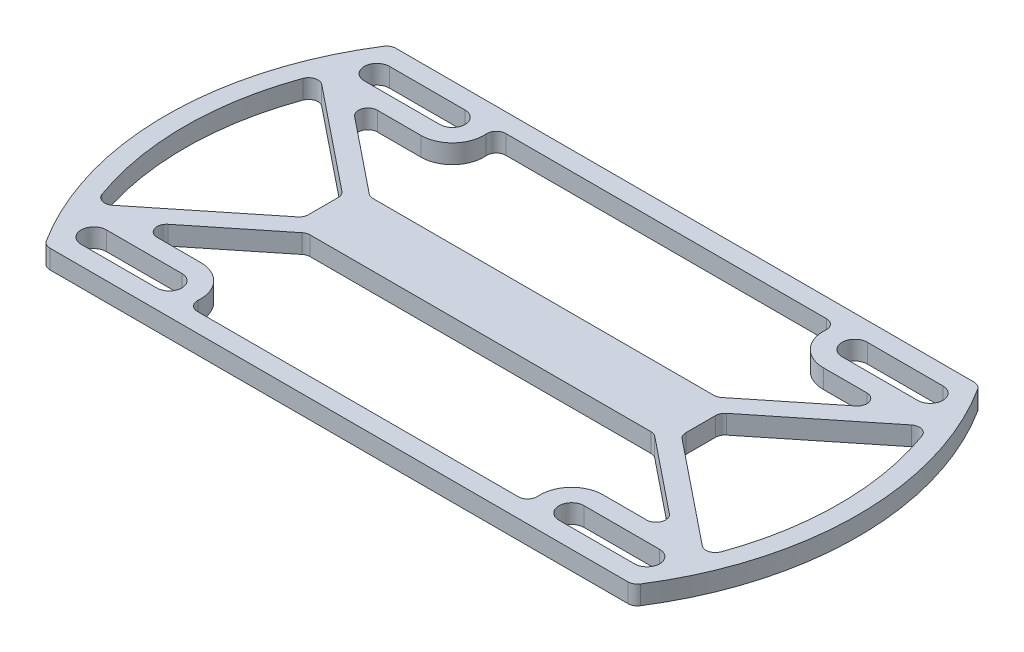
SolidWorks part; units mm, degrees
material "3.1355 (EN-AW 2024)"
ref_plane "Front" through (0, 0, 0) normal (0, 0, 1) x (1, 0, 0)
ref_plane "Top" through (0, 0, 0) normal (0, 1, 0) x (1, 0, 0)
ref_plane "Right" through (0, 0, 0) normal (1, 0, 0) x (0, 0, -1)
sketch "Эскиз1" plane through (0, 0, 0) normal (0, 1, 0) x (1, 0, 0)
  line L0 (9.8908, 3) -> (100.1092, 3)
  line L1 (0, 0) -> (8.2418, 0) construction
  line L2 (0, 0) -> (0, 55) construction
  line L3 (0, 55) -> (8.2418, 55) construction
  line L4 (110, 0) -> (110, 55) construction
  line L5 (9.8908, 52) -> (100.1092, 52)
  line L8 (110, 27.5) -> (0, 27.5) construction
  line L9 (8.2418, 0) -> (101.7582, 0)
  line L11 (8.2418, 55) -> (101.7582, 55)
  line L13 (55, 55) -> (55, 0) construction
  arc A0 (8.2418, 55) -> (8.2418, 0) centre (50, 27.5) ccw
  arc A1 (101.7582, 55) -> (101.7582, 0) centre (60, 27.5) cw
  arc A2 (9.8908, 52) -> (9.8908, 3) centre (50, 27.5) ccw
  arc A3 (100.1092, 52) -> (100.1092, 3) centre (60, 27.5) cw
  point P14 (55, 27.5)
  point P20 (55, 55)
  point P22 (55, 0)
  dimension "D4" = 50
  dimension "D1" = 55
  dimension "D2" = 110
  dimension "D3" = 3
extrude "Бобышка-Вытянуть1" add sketch "Эскиз1" along normal blind 3
sketch "Эскиз3" plane through (0, 0, 0) normal (0, -1, 0) x (1, 0, 0)
  line L0 (25, -32.5) -> (85, -22.5) construction
  line L1 (85, -32.5) -> (25, -32.5)
  line L2 (85, -32.5) -> (85, -22.5)
  line L3 (85, -22.5) -> (25, -22.5)
  line L4 (25, -32.5) -> (25, -22.5)
  line L5 (55, 0) -> (55, -55) construction
  line L10 (8.2418, 0) -> (101.7582, 0) construction
  line L11 (101.7582, -55) -> (8.2418, -55) construction
  point P10 (55, -27.5)
  dimension "D1" = 10
  dimension "D2" = 60
extrude "Бобышка-Вытянуть3" add sketch "Эскиз3" against normal through all separate body
sketch "Эскиз4" plane through (0, 0, 0) normal (0, -1, 0) x (1, 0, 0)
  line L0 (11.0289, -5) -> (23.0289, -5) construction
  line L1 (11.0289, -3) -> (23.0289, -3)
  line L2 (11.0289, -7) -> (23.0289, -7)
  line L3 (9.8908, -3) -> (100.1092, -3) construction
  line L4 (55, 0) -> (55, -55) construction
  line L5 (8.2418, 0) -> (101.7582, 0) construction
  line L6 (101.7582, -55) -> (8.2418, -55) construction
  line L7 (0, -27.5) -> (110, -27.5) construction
  line L8 (11.0289, -3) -> (9.8908, -3)
  line L9 (11.0289, -10) -> (23.0289, -10)
  line L10 (9.8908, -3) -> (27.6114, -3)
  line L11 (11.0289, 0) -> (23.0289, 0) construction
  line L12 (98.9711, -5) -> (86.9711, -5) construction
  line L13 (98.9711, -3) -> (86.9711, -3)
  line L14 (98.9711, -7) -> (86.9711, -7)
  line L15 (100.1092, -3) -> (82.3886, -3)
  line L16 (98.9711, -10) -> (86.9711, -10)
  line L17 (98.9711, -3) -> (100.1092, -3)
  line L18 (11.0289, -50) -> (23.0289, -50) construction
  line L19 (11.0289, -52) -> (23.0289, -52)
  line L20 (11.0289, -48) -> (23.0289, -48)
  line L21 (98.9711, -50) -> (86.9711, -50) construction
  line L22 (98.9711, -52) -> (86.9711, -52)
  line L23 (98.9711, -48) -> (86.9711, -48)
  line L24 (98.9711, -52) -> (100.1092, -52)
  line L25 (98.9711, -45) -> (86.9711, -45)
  line L26 (100.1092, -52) -> (82.3886, -52)
  line L27 (9.8908, -52) -> (27.6114, -52)
  line L28 (11.0289, -45) -> (23.0289, -45)
  line L29 (11.0289, -52) -> (9.8908, -52)
  arc A0 (11.0289, -3) -> (11.0289, -7) centre (11.0289, -5) ccw
  arc A1 (23.0289, -7) -> (23.0289, -3) centre (23.0289, -5) ccw
  arc A2 (9.8908, -3) -> (9.8908, -52) centre (50, -27.5) ccw construction
  arc A3 (8.2418, 0) -> (8.2418, -55) centre (50, -27.5) ccw construction
  arc A4 (101.7582, -55) -> (101.7582, 0) centre (60, -27.5) ccw construction
  arc A5 (23.0289, -10) -> (27.6114, -3) centre (23.0289, -5) ccw
  arc A6 (7.1601, -8.1675) -> (11.0289, -10) centre (11.0289, -5) ccw
  arc A7 (9.8908, -3) -> (7.1601, -8.1675) centre (50, -27.5) ccw
  arc A8 (98.9711, -3) -> (98.9711, -7) centre (98.9711, -5) cw
  arc A9 (11.0289, 0) -> (11.0289, -10) centre (11.0289, -5) ccw construction
  arc A10 (23.0289, -10) -> (23.0289, 0) centre (23.0289, -5) ccw construction
  arc A11 (86.9711, -7) -> (86.9711, -3) centre (86.9711, -5) cw
  arc A12 (100.1092, -3) -> (102.8399, -8.1675) centre (60, -27.5) cw
  arc A13 (102.8399, -8.1675) -> (98.9711, -10) centre (98.9711, -5) cw
  arc A14 (86.9711, -10) -> (82.3886, -3) centre (86.9711, -5) cw
  arc A15 (11.0289, -52) -> (11.0289, -48) centre (11.0289, -50) cw
  arc A16 (23.0289, -48) -> (23.0289, -52) centre (23.0289, -50) cw
  arc A17 (98.9711, -52) -> (98.9711, -48) centre (98.9711, -50) ccw
  arc A18 (86.9711, -48) -> (86.9711, -52) centre (86.9711, -50) ccw
  arc A19 (86.9711, -45) -> (82.3886, -52) centre (86.9711, -50) ccw
  arc A20 (102.8399, -46.8325) -> (98.9711, -45) centre (98.9711, -50) ccw
  arc A21 (100.1092, -52) -> (102.8399, -46.8325) centre (60, -27.5) ccw
  arc A22 (9.8908, -52) -> (7.1601, -46.8325) centre (50, -27.5) cw
  arc A23 (7.1601, -46.8325) -> (11.0289, -45) centre (11.0289, -50) cw
  arc A24 (23.0289, -45) -> (27.6114, -52) centre (23.0289, -50) cw
  point P2 (17.0289, -5)
  point P36 (92.9711, -5)
  point P51 (17.0289, -50)
  point P58 (92.9711, -50)
  arc M5 (9.8908, -52) -> (9.8908, -3) centre (50, -27.5) cw
  line M6 (9.8908, -3) -> (100.1092, -3)
  arc M7 (100.1092, -3) -> (100.1092, -52) centre (60, -27.5) cw
  line M8 (100.1092, -52) -> (9.8908, -52)
  dimension "D1" = 2
  dimension "D2" = 12
  dimension "D3" = 3
extrude "Бобышка-Вытянуть4" add sketch "Эскиз4" against normal through all contours A6 L9 A5 A1 L2 A0 M5 M6 | A0 M6 M5 | A14 L16 A13 A8 L14 A11 M7 M6 | A8 M6 M7 | A20 L25 A19 A18 L23 A17 M7 M8 | A17 M8 M7 | A24 L28 A23 A15 L20 A16 M5 M8 | A15 M8 M5 region at (10.0021, 0, -3.2088) region at (18.548, 0, -7.7057) region at (91.452, 0, -7.7057) region at (18.548, 0, -47.2943) region at (10.0021, 0, -51.7912) region at (99.9979, 0, -3.2088) region at (91.452, 0, -47.2943) region at (99.9979, 0, -51.7912)
sketch "Эскиз5" plane through (0, 0, 0) normal (0, -1, 0) x (1, 0, 0)
  line L0 (25, -22.5) -> (7.1601, -8.1675) construction
  line L1 (25, -32.5) -> (7.1601, -46.8325) construction
  line L2 (102.8399, -8.1675) -> (85, -22.5) construction
  line L3 (85, -32.5) -> (85, -22.5) construction
  line L4 (85, -32.5) -> (102.8399, -46.8325) construction
  line L5 (27.395, -22.5) -> (8.0996, -6.9981)
  line L6 (25, -30.5759) -> (6.2207, -45.6631)
  line L7 (101.9004, -6.9981) -> (82.605, -22.5)
  line L8 (82.605, -32.5) -> (101.9004, -48.0019)
  line L9 (25, -24.4241) -> (6.2207, -9.3369)
  line L10 (27.395, -32.5) -> (8.0996, -48.0019)
  line L11 (103.7793, -9.3369) -> (85, -24.4241)
  line L12 (85, -30.5759) -> (103.7793, -45.6631)
  line L13 (25.9395, -21.3306) -> (8.0996, -6.9981) construction
  line L14 (24.0605, -23.6694) -> (6.2207, -9.3369) construction
  line L15 (24.0605, -31.3306) -> (6.2207, -45.6631) construction
  line L16 (25.9395, -33.6694) -> (8.0996, -48.0019) construction
  line L17 (85, -32.5) -> (85, -22.5)
  line L18 (85, -22.5) -> (25, -22.5)
  line L19 (25, -22.5) -> (25, -32.5)
  line L20 (25, -32.5) -> (85, -32.5)
  line L21 (85, -32.5) -> (85, -30.5759)
  line L22 (85, -22.5) -> (82.605, -22.5)
  line L23 (25, -22.5) -> (25, -24.4241)
  line L24 (25, -32.5) -> (27.395, -32.5)
  line L25 (84.0605, -33.6694) -> (101.9004, -48.0019) construction
  line L26 (85.9395, -31.3306) -> (103.7793, -45.6631) construction
  line L27 (103.7793, -9.3369) -> (85.9395, -23.6694) construction
  line L28 (101.9004, -6.9981) -> (84.0605, -21.3306) construction
  line L29 (27.395, -22.5) -> (25, -22.5)
  line L30 (85, -24.4241) -> (85, -22.5)
  line L31 (82.605, -32.5) -> (85, -32.5)
  line L32 (25, -30.5759) -> (25, -32.5)
  line L33 (8.0996, -6.9981) -> (6.2207, -9.3369)
  line L34 (8.0996, -48.0019) -> (6.2207, -45.6631)
  line L35 (101.9004, -48.0019) -> (103.7793, -45.6631)
  line L36 (101.9004, -6.9981) -> (103.7793, -9.3369)
  dimension "D1" = 1.5
  dimension "D2" = 1.5
  dimension "D3" = 0
extrude "Бобышка-Вытянуть5" add sketch "Эскиз5" against normal through all
fillet "Скругление1" radius 1.5 20 edges at (103.4564, 1.5, -9.5963) (103.4564, 1.5, -45.4037) (85, 1.5, -24.4241) (85, 1.5, -30.5759) (25, 1.5, -24.4241) (25, 1.5, -30.5759) (6.5436, 1.5, -9.5963) (6.5436, 1.5, -45.4037) (27.6114, 1.5, -52) (11.8361, 1.5, -45) (82.3886, 1.5, -52) (98.1639, 1.5, -45) (82.605, 1.5, -32.5) (27.395, 1.5, -32.5) (82.605, 1.5, -22.5) (98.1639, 1.5, -10) (82.3886, 1.5, -3) (27.6114, 1.5, -3) (27.395, 1.5, -22.5) (11.8361, 1.5, -10)
fillet "Скругление2" radius 1.5 4 edges at (8.2418, 1.5, 0) (8.2418, 1.5, -55) (101.7582, 1.5, 0) (101.7582, 1.5, -55)
